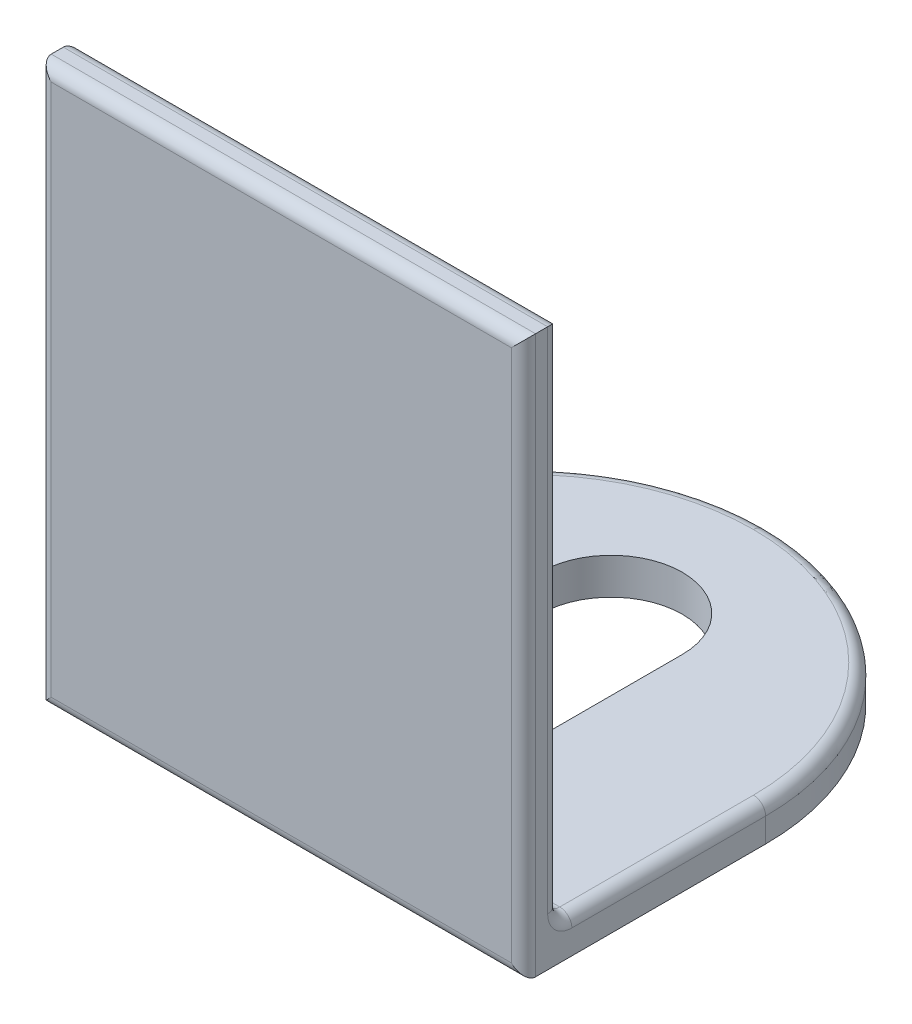
SolidWorks part; units mm, degrees
ref_plane "Front Plane" through (0, 0, 0) normal (0, 0, 1) x (1, 0, 0)
ref_plane "Top Plane" through (0, 0, 0) normal (0, 1, 0) x (1, 0, 0)
ref_plane "Right Plane" through (0, 0, 0) normal (1, 0, 0) x (0, 0, -1)
sketch "Sketch2" plane through (0, 0, 0) normal (0, 1, 0) x (1, 0, 0)
  line L1 (-20, -20) -> (20, -20)
  line L2 (-20, -20) -> (-20, 20)
  line L3 (-20, 20) -> (20, 20)
  line L4 (20, -20) -> (20, 20)
  line L5 (-20, -20) -> (20, 20) construction
  line L6 (-20, 20) -> (20, -20) construction
  point P0 (0, 0)
  point P6 (-20, 0)
  dimension "D1" = 40
  dimension "D2" = 40
extrude "Boss-Extrude1" add sketch "Sketch2" along normal blind 3
sketch "Sketch4" plane through (0, 3, 0) normal (0, 1, 0) x (1, 0, 0)
  line L0 (20, -20) -> (20, 20) construction
  line L1 (-20, -20) -> (20, -20)
  line L2 (-20, -20) -> (-20, -17)
  line L3 (-20, -17) -> (20, -17)
  line L4 (20, -20) -> (20, -17)
  dimension "D1" = 3
extrude "Boss-Extrude2" add sketch "Sketch4" along normal blind 43
fillet "Fillet3" radius 20 2 edges at (20, 1.5, -20) (-20, 1.5, -20)
sketch "Sketch5" plane through (0, 0, 0) normal (0, -1, 0) x (1, 0, 0)
  line L0 (6, -7.1209) -> (6, 5.3059)
  line L1 (-5.7571, -7.1209) -> (-5.7571, 6.9958)
  arc A0 (6, -7.1209) -> (-5.7571, -7.1209) centre (0.1214, -7.1209) cw
  arc A1 (6, 5.3059) -> (-5.7571, 6.9958) centre (0.2429, 6.9958) ccw
  point P6 (0.1214, -12.9994)
  dimension "D1" = 6
  dimension "D2" = 6
  dimension "D3" = 13
  dimension "D4" = 7
extrude "Cut-Extrude1" cut sketch "Sketch5" against normal blind 37
fillet "Fillet4" radius 1 12 edges at (14.1421, 3, -14.1421) (-14.1421, 3, -14.1421) (20, 3, 8.5) (-20, 3, 8.5) (20, 24.5, 17) (0, 46, 17) (-20, 24.5, 17) (0, 3, 17) (-20, 23, 20) (0, 46, 20) (20, 23, 20) (0, 0, 20)
